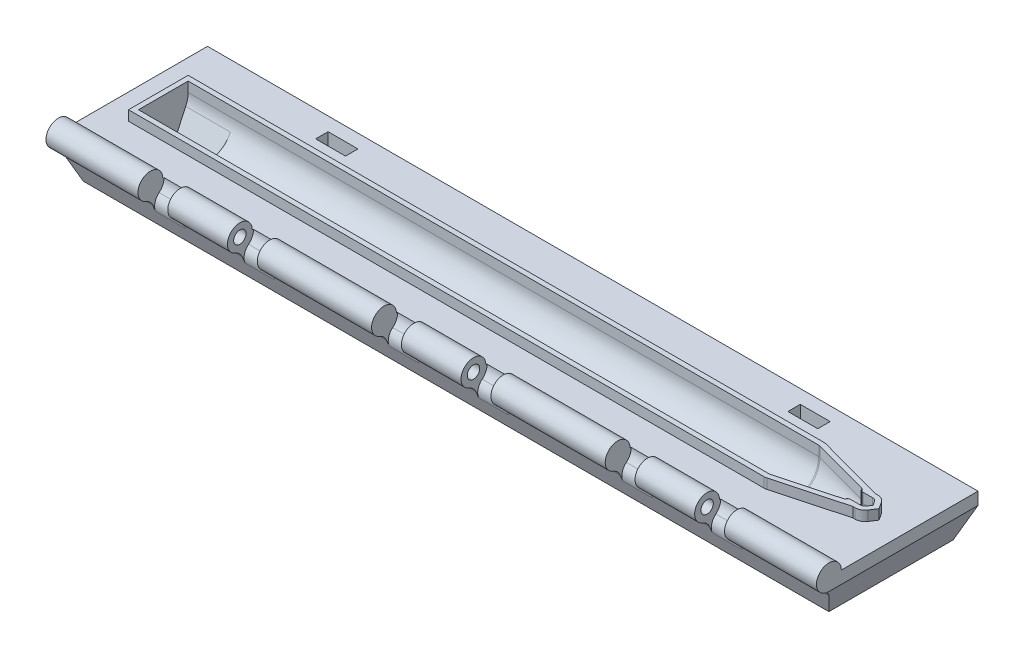
SolidWorks part; units mm, degrees
note: The reader was unsure of these and kept them because the rebuilt part matched: shared geometry of "Sketch3<2>", "Sketch3<3>".
ref_plane "Front Plane" through (0, 0, 0) normal (0, 0, 1) x (1, 0, 0)
ref_plane "Top Plane" through (0, 0, 0) normal (0, 1, 0) x (1, 0, 0)
ref_plane "Right Plane" through (0, 0, 0) normal (1, 0, 0) x (0, 0, -1)
sketch "Sketch1" plane through (0, 0, 0) normal (0, 1, 0) x (1, 0, 0)
  line L1 (77.5, -15) -> (-77.5, -15)
  line L2 (77.5, -15) -> (77.5, 15)
  line L3 (77.5, 15) -> (-77.5, 15)
  line L4 (-77.5, -15) -> (-77.5, 15)
  line L5 (77.5, -15) -> (-77.5, 15) construction
  line L6 (77.5, 15) -> (-77.5, -15) construction
  point P0 (0, 0)
  dimension "D1" = 155
  dimension "D2" = 30
extrude "Boss-Extrude1" add sketch "Sketch1" along normal blind 8.5 from offset 1.5
sketch "Sketch2" plane through (-77.5, 0, 0) normal (-1, 0, 0) x (0, 0, 1)
  circle A0 centre (15, 10) radius 2.5
  dimension "D1" = 5
extrude "Boss-Extrude2" add sketch "Sketch2" against normal through all
sketch "Sketch3" plane through (0, 0, 0) normal (1, 0, 0) x (0, 0, -1)
  circle A0 centre (-15, 10) radius 2.75
  dimension "D1" = 5.5
extrude "Cut-Extrude1" cut sketch "Sketch3" along normal blind 6 from offset 6
mirror "Mirror1" about plane through (0, 0, 0) normal (1, 0, 0) of "Cut-Extrude1"
extrude "Cut-Extrude2" cut sketch "Sketch3<2>" along normal blind 6 from offset 35
sketch "Sketch3<2>" plane through (0, 0, 0) normal (1, 0, 0) x (0, 0, -1) same geometry as "Sketch3"
extrude "Cut-Extrude3" cut sketch "Sketch3<3>" along normal blind 6 from offset 53
sketch "Sketch3<3>" plane through (0, 0, 0) normal (1, 0, 0) x (0, 0, -1) same geometry as "Sketch3"
mirror "Mirror2" about plane through (0, 0, 0) normal (1, 0, 0) of "Cut-Extrude2", "Cut-Extrude3"
sketch "Sketch4" plane through (0, 0, 0) normal (1, 0, 0) x (0, 0, -1)
  circle A0 centre (-15, 10) radius 1.25
  dimension "D1" = 2.5
extrude "Cut-Extrude4" cut sketch "Sketch4" against normal mid plane 12
sketch "Sketch6" plane through (53, 0, 0) normal (1, 0, 0) x (0, 0, -1)
  circle A0 centre (-15, 10) radius 1.25
  dimension "D1" = 2.5
extrude "Cut-Extrude5" cut sketch "Sketch6" against normal up to next
mirror "Mirror3" about plane through (0, 0, 0) normal (1, 0, 0) of "Cut-Extrude5"
sketch "Sketch7" plane through (0, 10, 0) normal (0, 1, 0) x (1, 0, 0)
  line L0 (0, 0) -> (77.5, 0) construction
  line L1 (77.5, -12.5) -> (77.5, 15) construction
  line L2 (0, 0) -> (-77.5, 0) construction
  line L3 (-77.5, 15) -> (-77.5, -12.5) construction
  line L4 (-71.4, 0) -> (-71.4, -5)
  line L5 (-71.4, -5) -> (55.467, -5)
  line L6 (55.7284, -4.9652) -> (67.2307, -1.85)
  line L7 (67.6, -1.3674) -> (67.6, -1.75)
  line L8 (68.1, -1.25) -> (70.0527, -1.25)
  line L9 (70.895, -0.7891) -> (71.4, 0)
  line L10 (-71.4, 0) -> (71.4, 0)
  arc A0 (70.0527, -1.25) -> (70.895, -0.7891) centre (70.0527, -0.25) ccw
  arc A1 (68.1, -1.25) -> (67.6, -1.75) centre (68.1, -1.75) ccw
  arc A2 (67.2307, -1.85) -> (67.6, -1.3674) centre (67.1, -1.3674) ccw
  arc A3 (55.467, -5) -> (55.7284, -4.9652) centre (55.467, -4) ccw
  point P17 (70.6, -1.25)
  point P21 (67.6, -1.25)
  point P24 (67.6, -1.75)
  point P27 (55.6, -5)
  dimension "D8" = 1
  dimension "D9" = 3.8
  dimension "D10" = 0.5
  dimension "D11" = 0.5
  dimension "D12" = 1
  dimension "D1" = 5
  dimension "D2" = 127
  dimension "D3" = 6.1
  dimension "D4" = 12
  dimension "D5" = 3.25
  dimension "D6" = 1.25
  dimension "D7" = 3
revolve "Cut-Revolve1" cut sketch "Sketch7" angle 360 about L10
sketch "Sketch8" plane through (0, 10, 0) normal (0, 1, 0) x (1, 0, 0)
  line L0 (67.2307, 1.85) -> (55.7284, 4.9652) construction
  line L1 (55.467, 5) -> (-71.4, 5) construction
  line L2 (-71.4, 5) -> (-71.4, -5) construction
  line L3 (-71.4, -5) -> (55.467, -5) construction
  line L4 (55.7284, -4.9652) -> (67.2307, -1.85) construction
  line L5 (68.1, -1.25) -> (70.0527, -1.25) construction
  line L6 (70.0527, 1.25) -> (68.1, 1.25) construction
  line L7 (67.6, 1.75) -> (67.6, 1.3674) construction
  line L8 (71.4, 0) -> (70.895, 0.7891) construction
  line L9 (70.895, -0.7891) -> (71.4, 0) construction
  line L10 (67.6, -1.3674) -> (67.6, -1.75) construction
  line L11 (-71.4, 5) -> (-71.4, -5)
  line L12 (-71.4, -5) -> (55.467, -5)
  line L13 (55.467, 5) -> (-71.4, 5)
  line L14 (67.2307, 1.85) -> (55.7284, 4.9652)
  line L15 (70.0527, 1.25) -> (68.1, 1.25)
  line L16 (67.6, 1.75) -> (67.6, 1.3674)
  line L17 (71.4, 0) -> (70.895, 0.7891)
  line L18 (70.895, -0.7891) -> (71.4, 0)
  line L19 (68.1, -1.25) -> (70.0527, -1.25)
  line L20 (67.6, -1.3674) -> (67.6, -1.75)
  line L21 (55.7284, -4.9652) -> (67.2307, -1.85)
  arc A0 (68.1, -1.25) -> (67.6, -1.75) centre (68.1, -1.75) ccw construction
  arc A1 (67.2307, -1.85) -> (67.6, -1.3674) centre (67.1, -1.3674) ccw construction
  arc A2 (55.467, -5) -> (55.7284, -4.9652) centre (55.467, -4) ccw construction
  arc A3 (55.7284, 4.9652) -> (55.467, 5) centre (55.467, 4) ccw construction
  arc A4 (70.895, 0.7891) -> (70.0527, 1.25) centre (70.0527, 0.25) ccw construction
  arc A5 (70.0527, -1.25) -> (70.895, -0.7891) centre (70.0527, -0.25) ccw construction
  arc A6 (67.6, 1.3674) -> (67.2307, 1.85) centre (67.1, 1.3674) ccw construction
  arc A7 (67.6, 1.75) -> (68.1, 1.25) centre (68.1, 1.75) ccw construction
  arc A8 (55.467, -5) -> (55.7284, -4.9652) centre (55.467, -4) ccw
  arc A9 (55.7284, 4.9652) -> (55.467, 5) centre (55.467, 4) ccw
  arc A10 (70.895, 0.7891) -> (70.0527, 1.25) centre (70.0527, 0.25) ccw
  arc A11 (70.0527, -1.25) -> (70.895, -0.7891) centre (70.0527, -0.25) ccw
  arc A12 (67.6, 1.3674) -> (67.2307, 1.85) centre (67.1, 1.3674) ccw
  arc A13 (67.6, 1.75) -> (68.1, 1.25) centre (68.1, 1.75) ccw
  arc A14 (67.2307, -1.85) -> (67.6, -1.3674) centre (67.1, -1.3674) ccw
  arc A15 (68.1, -1.25) -> (67.6, -1.75) centre (68.1, -1.75) ccw
sketch "Sketch13" plane through (0, 10, 0) normal (0, 1, 0) x (1, 0, 0)
  line L11 (-71.4, 5) -> (-71.4, -5)
  line L12 (-71.4, -5) -> (55.467, -5)
  line L13 (55.467, 5) -> (-71.4, 5)
  line L14 (67.2307, 1.85) -> (55.7284, 4.9652)
  line L15 (70.0527, 1.25) -> (68.1, 1.25)
  line L16 (67.6, 1.75) -> (67.6, 1.3674)
  line L17 (71.4, 0) -> (70.895, 0.7891)
  line L18 (70.895, -0.7891) -> (71.4, 0)
  line L19 (68.1, -1.25) -> (70.0527, -1.25)
  line L20 (67.6, -1.3674) -> (67.6, -1.75)
  line L21 (55.7284, -4.9652) -> (67.2307, -1.85)
  line L22 (69.5792, 2.25) -> (55.9898, 5.9305)
  line L23 (55.467, 6) -> (-72.4, 6)
  line L24 (-72.4, 6) -> (-72.4, -6)
  line L25 (-72.4, -6) -> (55.467, -6)
  line L26 (55.9898, -5.9305) -> (69.5792, -2.25)
  line L27 (69.5792, -2.25) -> (70.0527, -2.25)
  line L28 (71.7373, -1.3281) -> (72.5873, 0)
  line L29 (72.5873, 0) -> (71.7373, 1.3281)
  line L30 (70.0527, 2.25) -> (69.5792, 2.25)
  line L31 (69.5792, 2.25) -> (55.9898, 5.9305)
  line L32 (55.467, 6) -> (-72.4, 6)
  line L33 (-72.4, 6) -> (-72.4, -6)
  line L34 (-72.4, -6) -> (55.467, -6)
  line L35 (55.9898, -5.9305) -> (69.5792, -2.25)
  line L36 (69.5792, -2.25) -> (70.0527, -2.25)
  line L37 (71.7373, -1.3281) -> (72.5873, 0)
  line L38 (72.5873, 0) -> (71.7373, 1.3281)
  line L39 (70.0527, 2.25) -> (69.5792, 2.25)
  arc A8 (55.467, -5) -> (55.7284, -4.9652) centre (55.467, -4) ccw
  arc A9 (55.7284, 4.9652) -> (55.467, 5) centre (55.467, 4) ccw
  arc A10 (70.895, 0.7891) -> (70.0527, 1.25) centre (70.0527, 0.25) ccw
  arc A11 (70.0527, -1.25) -> (70.895, -0.7891) centre (70.0527, -0.25) ccw
  arc A12 (67.6, 1.3674) -> (67.2307, 1.85) centre (67.1, 1.3674) ccw
  arc A13 (67.6, 1.75) -> (68.1, 1.25) centre (68.1, 1.75) ccw
  arc A14 (67.2307, -1.85) -> (67.6, -1.3674) centre (67.1, -1.3674) ccw
  arc A15 (68.1, -1.25) -> (67.6, -1.75) centre (68.1, -1.75) ccw
  arc A16 (55.9898, 5.9305) -> (55.467, 6) centre (55.467, 4) ccw
  arc A17 (55.467, -6) -> (55.9898, -5.9305) centre (55.467, -4) ccw
  arc A18 (70.0527, -2.25) -> (71.7373, -1.3281) centre (70.0527, -0.25) ccw
  arc A19 (71.7373, 1.3281) -> (70.0527, 2.25) centre (70.0527, 0.25) ccw
  arc A20 (55.9898, 5.9305) -> (55.467, 6) centre (55.467, 4) ccw
  arc A21 (55.467, -6) -> (55.9898, -5.9305) centre (55.467, -4) ccw
  arc A22 (70.0527, -2.25) -> (71.7373, -1.3281) centre (70.0527, -0.25) ccw
  arc A23 (71.7373, 1.3281) -> (70.0527, 2.25) centre (70.0527, 0.25) ccw
  dimension "D1" = 1
extrude "Boss-Extrude3" add sketch "Sketch13" along normal blind 2
sketch "Sketch9" plane through (-71.4, 0, 0) normal (1, 0, 0) x (0, 0, -1)
  line L0 (-1.7015, 3) -> (-4.4684, 7.7565)
  line L1 (0, 5) -> (0, 3) construction
  line L2 (2.2985, 3) -> (-1.7015, 3)
  line L3 (2.2985, 3) -> (4.5849, 8.0053)
  line L4 (-4.4684, 7.7565) -> (4.5849, 8.0053)
  arc A1 (-5, 10) -> (5, 10) centre (0, 10) ccw construction
  dimension "D1" = 4
  dimension "D2" = 2
  dimension "D3" = 5.5028
  dimension "D4" = 2.7669
extrude "Cut-Extrude6" cut sketch "Sketch9" along normal blind 9
sketch "Sketch10" plane through (-77.5, 0, 0) normal (-1, 0, 0) x (0, 0, 1)
  line L0 (15, 7.5) -> (12.5, 1.5)
  line L1 (-15, 1.5) -> (15, 1.5) construction
  line L2 (12.5, 1.5) -> (15, 1.5)
  line L3 (15, 1.5) -> (15, 7.5)
  line L4 (15, 7.5) -> (-15, 7.5) construction
  line L5 (-15, 10) -> (-15, 1.5) construction
  line L6 (-15, 7.5) -> (-12.5, 1.5)
  line L7 (-12.5, 1.5) -> (-15, 1.5)
  line L8 (-15, 1.5) -> (-15, 7.5)
  dimension "D1" = 2.5
  dimension "D2" = 2.5
extrude "Cut-Extrude7" cut sketch "Sketch10" against normal through all
fillet "Fillet4" radius 2.5 1 edges at (-68.25, 7.5, 15)
fillet "Fillet5" radius 2.5 6 edges at (56, 7.2577, 15.2059) (38, 7.2577, 15.2059) (9, 7.2577, 15.2059) (-9, 7.2577, 15.2059) (-38, 7.2577, 15.2059) (-56, 7.2577, 15.2059)
sketch "Sketch11" plane through (0, 0, -15) normal (0, 0, -1) x (-1, 0, 0)
  line L0 (77.5, 7.5) -> (75, 1.5)
  line L1 (-77.5, 1.5) -> (77.5, 1.5) construction
  line L2 (75, 1.5) -> (77.5, 1.5)
  line L3 (77.5, 1.5) -> (77.5, 7.5)
  dimension "D1" = 2.5
extrude "Cut-Extrude8" cut sketch "Sketch11" against normal through all
mirror "Mirror4" about plane through (0, 0, 0) normal (1, 0, 0) of "Cut-Extrude8"
sketch "Sketch14" plane through (0, 0, -4.388) normal (-1, 0, 0) x (0, 0, -1)
  line L0 (5.362, -10) -> (7.862, -10)
  line L1 (7.812, -6.7494) -> (7.862, -4.75) construction
  line L4 (6.112, -10) -> (6.112, -4.75)
  line L5 (5.362, -4.75) -> (5.362, -10)
  line L12 (7.862, -4.75) -> (5.362, -4.75)
  line L13 (8.562, -6.75) -> (7.862, -4.75)
  line L14 (8.039, -6.9544) -> (8.562, -6.75)
  line L15 (7.862, -10) -> (7.862, -7.1442)
  line L16 (-16.888, -10) -> (10.612, -10) construction
  line L18 (10.612, -10) -> (10.612, -7.5) construction
  arc A4 (7.862, -7.1442) -> (8.039, -6.9544) centre (8.1483, -7.2338) cw
  dimension "D8" = 0.3
  dimension "D1" = 2.5
  dimension "D2" = 5.25
  dimension "D3" = 2.8558
  dimension "D4" = 2
  dimension "D5" = 0.2044
  dimension "D6" = 0.7
  dimension "D7" = 0.75
  dimension "D9" = 2
  dimension "D10" = 0.75
  dimension "D11" = 2.75
extrude "Cut-Extrude9" cut sketch "Sketch14" against normal blind 6 from offset 44.5 contours L5 L0 L15 A4 L14 L13 L12 offset against normal yes
mirror "Mirror5" about plane through (0, 0, 0) normal (1, 0, 0) of "Cut-Extrude9"
